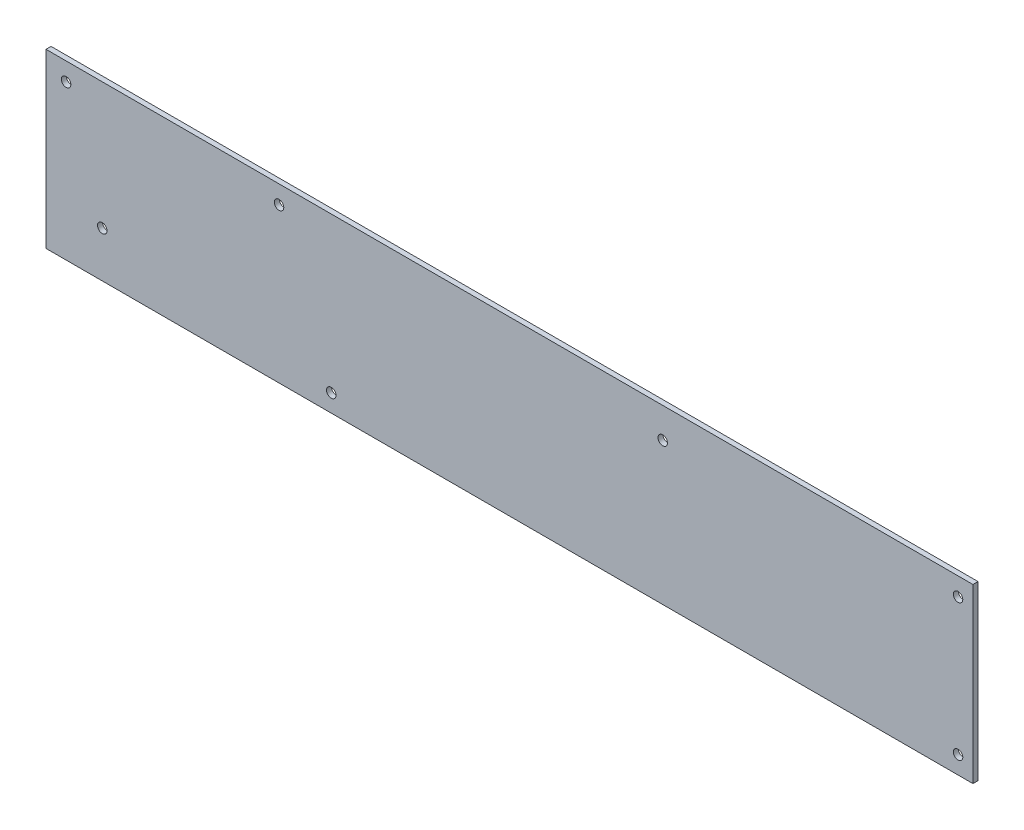
SolidWorks part; units mm, degrees
ref_plane "Front Plane" through (0, 0, 0) normal (0, 0, 1) x (1, 0, 0)
ref_plane "Top Plane" through (0, 0, 0) normal (0, 1, 0) x (1, 0, 0)
ref_plane "Right Plane" through (0, 0, 0) normal (1, 0, 0) x (0, 0, -1)
sketch "Sketch2" plane through (0, 0, 0) normal (0, 0, 1) x (1, 0, 0)
  line L1 (146.5, -27.26) -> (-146.5, -27.26)
  line L2 (146.5, -27.26) -> (146.5, 27.26)
  line L3 (146.5, 27.26) -> (-146.5, 27.26)
  line L4 (-146.5, -27.26) -> (-146.5, 27.26)
  line L5 (146.5, -27.26) -> (-146.5, 27.26) construction
  line L6 (146.5, 27.26) -> (-146.5, -27.26) construction
  point P0 (0, 0)
  dimension "D1" = 293
  dimension "D2" = 54.52
extrude "ExtrudedBase_PCB" add sketch "Sketch2" along normal blind 1.6
sketch "Sketch3" plane through (0, 0, 1.6) normal (0, 0, 1) x (1, 0, 0)
  line L0 (-146.5, 27.26) -> (-146.5, -27.26) construction
  line L2 (-146.5, -27.26) -> (146.5, -27.26) construction
  circle A0 centre (-140.15, 21.508) radius 1.5
  circle A1 centre (-72.84, 21.508) radius 1.5
  circle A2 centre (48.445, 17.698) radius 1.5
  circle A3 centre (141.79, 21.508) radius 1.5
  circle A4 centre (-128.72, -12.782) radius 1.5
  circle A5 centre (-56.33, -21.672) radius 1.5
  circle A6 centre (141.79, -21.672) radius 1.5
  point P20 (131.6558, -21.3505)
  dimension "D1" = 6.35
  dimension "D3" = 73.66
  dimension "D2" = 44.958
  dimension "D4" = 288.29
  dimension "D5" = 14.478
  dimension "D6" = 194.945
  dimension "D7" = 48.768
  dimension "D8" = 5.588
  dimension "D9" = 5.588
  dimension "D10" = 288.29
  dimension "D11" = 17.78
  dimension "D12" = 90.17
extrude "ExtrudedCut_MountingHoles" cut sketch "Sketch3" against normal through all
